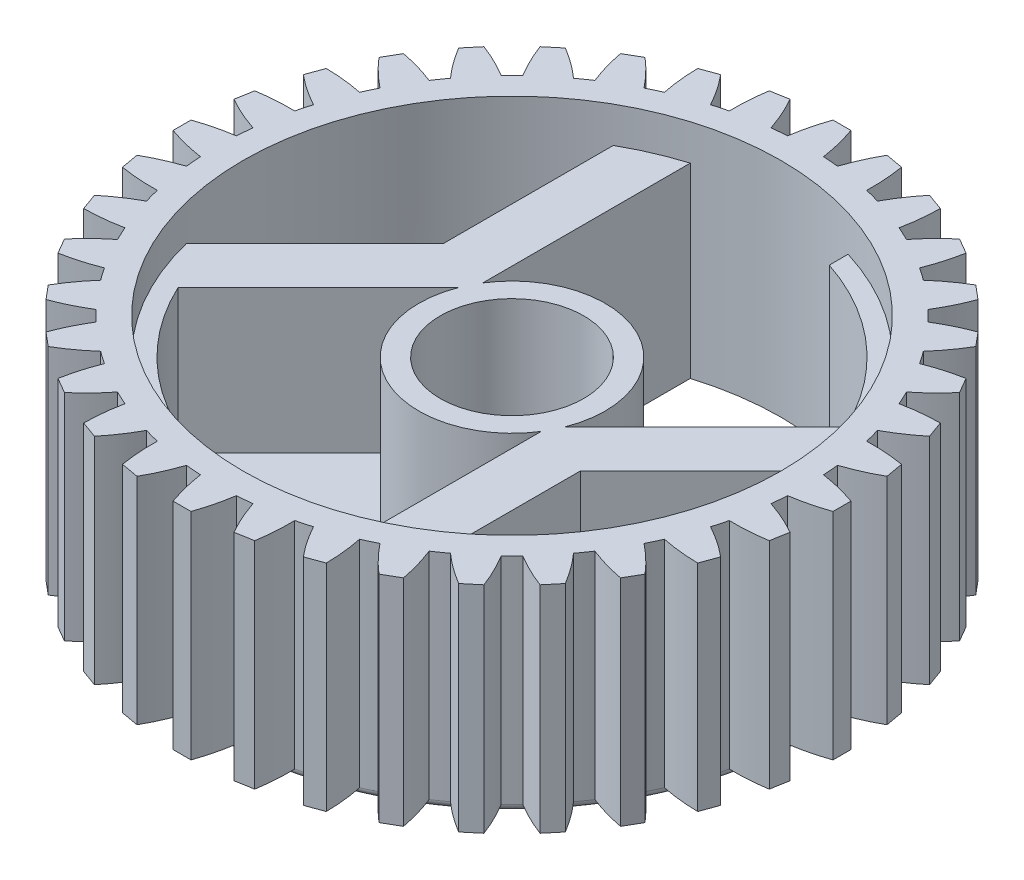
SolidWorks part; units mm, degrees
ref_plane "前视基准面" through (0, 0, 0) normal (0, 0, 1) x (1, 0, 0)
ref_plane "上视基准面" through (0, 0, 0) normal (0, 1, 0) x (1, 0, 0)
ref_plane "右视基准面" through (0, 0, 0) normal (1, 0, 0) x (0, 0, -1)
sketch "草图1" plane through (0, 0, 0) normal (0, 1, 0) x (1, 0, 0)
  circle A0 centre (0, 0) radius 8.2
  dimension "D1" = 16.4
extrude "凸台-拉伸1" add sketch "草图1" along normal blind 6.2
sketch "草图2" plane through (0, 6.2, 0) normal (0, 1, 0) x (1, 0, 0)
  circle A0 centre (0, 0) radius 7.5
  dimension "D1" = 15
extrude "切除-拉伸1" cut sketch "草图2" against normal blind 5
sketch "草图3" plane through (0, 1.2, 0) normal (0, 1, 0) x (1, 0, 0)
  line L0 (0, 7.5) -> (0, -7.5) construction
  line L1 (-2.2, 7.1701) -> (-2.2, 2.7)
  line L2 (2.2, 7.1701) -> (2.2, 2.7)
  line L3 (-2.2, 0) -> (2.2, 0) construction
  line L4 (-2.2, 7.5) -> (-2.2, -7.5) construction
  line L5 (2.2, 7.5) -> (2.2, -7.5) construction
  line L6 (-2.2, -2.7) -> (2.2, -2.7)
  line L7 (-2.2, 2.7) -> (2.2, 2.7)
  line L8 (-2.2, -2.7) -> (-2.2, -7.1701)
  line L9 (2.2, -2.7) -> (2.2, -7.1701)
  circle A0 centre (0, 0) radius 2
  circle A1 centre (0, 0) radius 7.5 construction
  arc A2 (2.2, 7.1701) -> (-2.2, 7.1701) centre (0, 0) ccw
  arc A3 (-2.2, -7.1701) -> (2.2, -7.1701) centre (0, 0) ccw
  dimension "D1" = 4
  dimension "D2" = 2.2
  dimension "D3" = 2.2
  dimension "D4" = 2.7
  dimension "D5" = 2.7
extrude "切除-拉伸2" cut sketch "草图3" against normal through all
sketch "草图4" plane through (0, 1.2, 0) normal (0, 1, 0) x (1, 0, 0)
  line L0 (2.2, -7.1701) -> (2.2, -1.3856)
  line L1 (3.7, -6.5238) -> (3.7, -1.7914)
  line L2 (2.4203, -0.9498) -> (6.3391, 2.9691)
  line L3 (3.7, -7.1701) -> (3.7, -1.1701) construction
  line L4 (3.7, -1.7914) -> (7.2829, 1.7915)
  line L5 (2.2, 7.1701) -> (2.2, 6.6453)
  line L6 (2.2, 2.7) -> (2.2, 7.1701) construction
  line L8 (2.2, -1.1701) -> (9.1336, 5.7635) construction
  line L9 (3.2607, -2.2307) -> (10.1942, 4.7028) construction
  line L10 (2.2, -7.1701) -> (2.2, -1.1701) construction
  circle A0 centre (0, 0) radius 2
  arc A1 (2.4203, -0.9498) -> (2.2, -1.3856) centre (0, 0) ccw
  arc A2 (7.2829, 1.7915) -> (2.2, 7.1701) centre (0, 0) ccw
  arc A3 (6.3391, 2.9691) -> (2.2, 6.6453) centre (0, 0) ccw
  arc A4 (2.2, -7.1701) -> (3.7, -6.5238) centre (0, 0) ccw
  dimension "D1" = 4
  dimension "D2" = 5.2
  dimension "D6" = 135
  dimension "D7" = 1.5
extrude "凸台-拉伸2" add sketch "草图4" along normal blind 4
pattern_circular "阵列(圆周)1" count 2 over 360 about axis through (0, 1.2, 0) along (0, 1, 0) of "凸台-拉伸2"
sketch "草图5" plane through (0, 6.2, 0) normal (0, 1, 0) x (1, 0, 0)
  line L0 (0, 8.2) -> (0, 9.2) construction
  line L1 (0.25, 9.2) -> (-0.25, 9.2)
  line L2 (0, 8.7) -> (-0.4, 8.7) construction
  line L3 (0, 8.2) -> (-0.5, 8.2) construction
  circle A0 centre (0, 0) radius 8.2 construction
  arc A1 (0.5023, 8.1846) -> (-0.5023, 8.1846) centre (0, 0) ccw
  arc A2 (-0.25, 9.2) -> (-0.5023, 8.1846) centre (4.925, 7.375) ccw
  arc A3 (0.25, 9.2) -> (0.5023, 8.1846) centre (-4.925, 7.375) cw
  dimension "D5" = 16.4
  dimension "D1" = 1
  dimension "D2" = 0.25
  dimension "D3" = 0.4
  dimension "D4" = 0.5
extrude "凸台-拉伸3" add sketch "草图5" against normal blind 6
pattern_circular "阵列(圆周)2" count 36 over 360 about axis through (0, 1.2, 0) along (0, 1, 0) of "凸台-拉伸3"
fillet "圆角1" radius 0.2 1 edges at (0, 0, 8.2)
